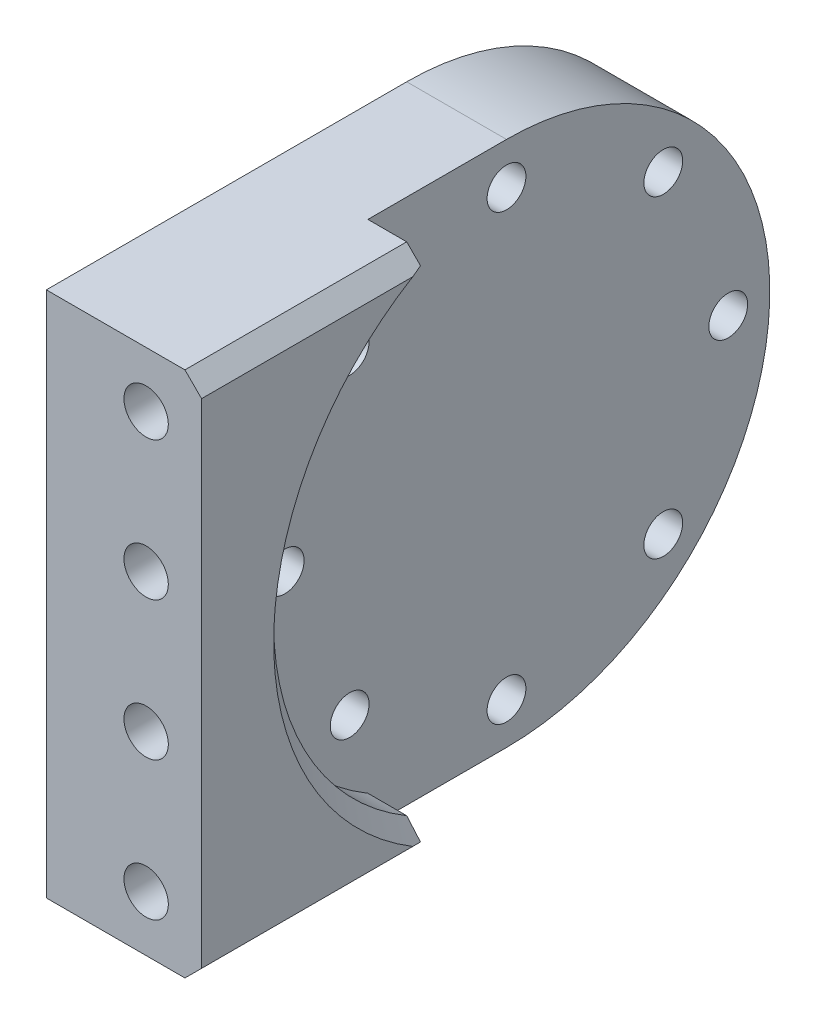
SolidWorks part; units mm, degrees
ref_plane "前视基准面" through (0, 0, 0) normal (0, 0, 1) x (1, 0, 0)
ref_plane "上视基准面" through (0, 0, 0) normal (0, 1, 0) x (1, 0, 0)
ref_plane "右视基准面" through (0, 0, 0) normal (1, 0, 0) x (0, 0, -1)
other "Configuration Table"
sketch "草图1" plane through (0, 0, 0) normal (1, 0, 0) x (0, 0, -1)
  line L0 (0, 0) -> (65, 0) construction
  line L1 (65, 47.5) -> (0, 47.5)
  line L2 (0, 47.5) -> (0, -47.5)
  line L3 (65, -47.5) -> (0, -47.5)
  arc A0 (65, -47.5) -> (65, 47.5) centre (65, 0) ccw
  dimension "D2" = 47.5
  dimension "D1" = 65
extrude "凸台-拉伸1" add sketch "草图1" along normal blind 28
sketch "草图2" plane through (28, 0, 0) normal (1, 0, 0) x (0, 0, -1)
  circle A0 centre (65, 0) radius 49
  dimension "D1" = 98
extrude "切除-拉伸1" cut sketch "草图2" against normal blind 10
sketch "草图3" plane through (18, 0, 0) normal (1, 0, 0) x (0, 0, -1)
  circle A0 centre (65, 0) radius 40 construction
  circle A1 centre (65, 40) radius 3.5
  circle A2 centre (93.2843, 28.2843) radius 3.5
  circle A3 centre (105, 0) radius 3.5
  circle A4 centre (93.2843, -28.2843) radius 3.5
  circle A5 centre (65, -40) radius 3.5
  circle A6 centre (36.7157, -28.2843) radius 3.5
  circle A7 centre (25, 0) radius 3.5
  circle A8 centre (36.7157, 28.2843) radius 3.5
  point P6 (105, 0)
  point P21 (65, 0)
  dimension "D1" = 80
  dimension "D2" = 7
  dimension "D3" = 8
extrude "切除-拉伸2" cut sketch "草图3" against normal up to next
sketch "草图4" plane through (28, 0, 0) normal (1, 0, 0) x (0, 0, -1)
  line L0 (0, 47.5) -> (0, -47.5) construction
  line L1 (40, 50) -> (70, 50)
  line L2 (40, 50) -> (40, -50)
  line L3 (40, -50) -> (70, -50)
  line L4 (70, 50) -> (70, -50)
  line L5 (40, 50) -> (70, -50) construction
  line L6 (40, -50) -> (70, 50) construction
  point P0 (55, 0)
  point P5 (0, 0)
  dimension "D1" = 30
  dimension "D2" = 40
  dimension "D3" = 100
extrude "切除-拉伸3" cut sketch "草图4" against normal up to surface (10 mm away) up to face at (18, 40, -68.5)
sketch "草图5" plane through (0, 0, 0) normal (0, 0, 1) x (1, 0, 0)
  line L0 (0, 0) -> (28, 0) construction
  line L1 (28, 47.5) -> (28, -47.5) construction
  circle A0 centre (18, 37.5) radius 4
  circle A1 centre (18, 12.5) radius 4
  circle A2 centre (18, -12.5) radius 4
  circle A3 centre (18, -37.5) radius 4
  point P13 (0, 0)
  dimension "D1" = 8
  dimension "D3" = 75
  dimension "D2" = 25
  dimension "D4" = 10
extrude "切除-拉伸4" cut sketch "草图5" against normal blind 15
chamfer "倒角1" distance 3 angle 45 3 edges at (28, -47.5, -20) (28, 47.5, -20) (28, 0, -16)
